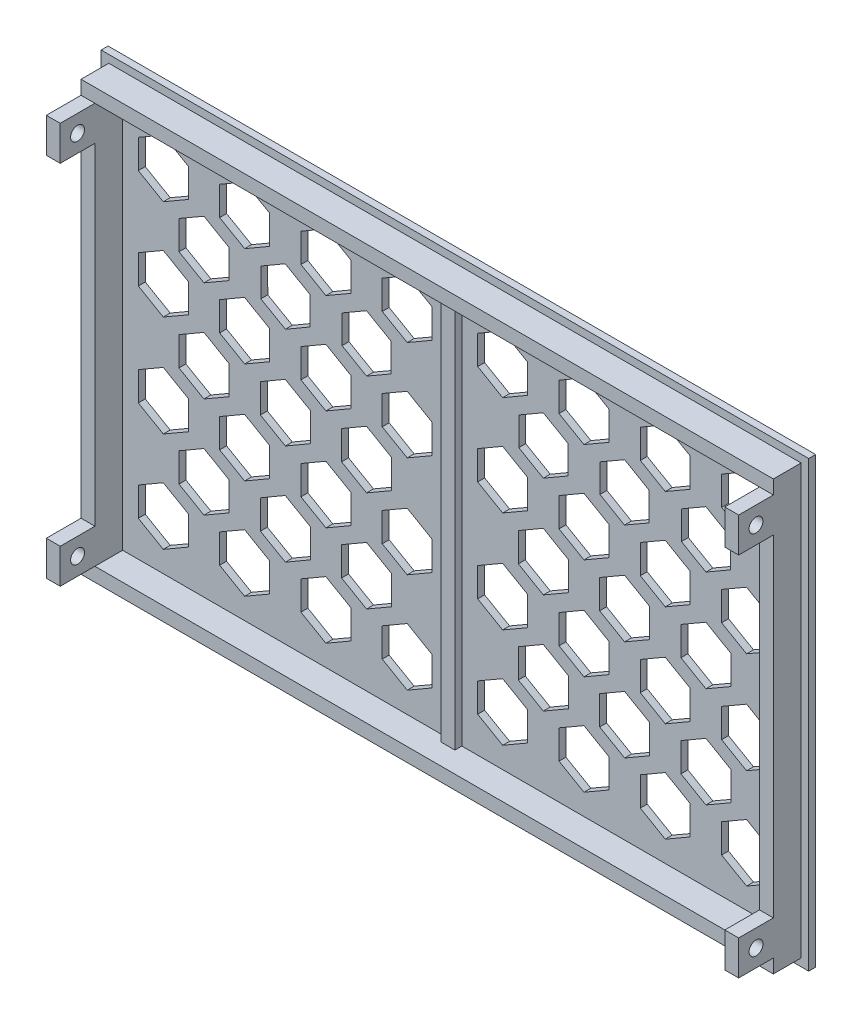
SolidWorks part; units mm, degrees
ref_plane "Спереди" through (0, 0, 0) normal (0, 0, 1) x (1, 0, 0)
ref_plane "Сверху" through (0, 0, 0) normal (0, 1, 0) x (1, 0, 0)
ref_plane "Справа" through (0, 0, 0) normal (1, 0, 0) x (0, 0, -1)
sketch "Эскиз1" plane through (0, 0, 0) normal (0, 0, 1) x (1, 0, 0)
  line L0 (-41.023, 20.2512) -> (60.977, 20.2512)
  line L1 (60.977, 20.2512) -> (60.977, -43.7488)
  line L2 (60.977, -43.7488) -> (-41.023, -43.7488)
  line L3 (-41.023, -43.7488) -> (-41.023, 20.2512)
  line L4 (-39.923, -42.6488) -> (-39.923, 19.1512)
  line L5 (-39.923, 19.1512) -> (59.877, 19.1512)
  line L6 (59.877, 19.1512) -> (59.877, -42.6488)
  line L7 (59.877, -42.6488) -> (-39.923, -42.6488)
  line L8 (-37.923, -40.6488) -> (-37.923, 17.1512)
  line L9 (-37.923, 17.1512) -> (57.877, 17.1512)
  line L10 (57.877, 17.1512) -> (57.877, -40.6488)
  line L11 (57.877, -40.6488) -> (-37.923, -40.6488)
  line L12 (57.877, -40.6488) -> (59.877, -40.6488)
  line L13 (59.877, -40.6488) -> (59.877, -35.6488)
  line L14 (59.877, -35.6488) -> (57.877, -35.6488)
  line L15 (57.877, -35.6488) -> (57.877, -40.6488)
  line L16 (57.877, 17.1512) -> (59.877, 17.1512)
  line L17 (59.877, 17.1512) -> (59.877, 12.1512)
  line L18 (59.877, 12.1512) -> (57.877, 12.1512)
  line L19 (57.877, 12.1512) -> (57.877, 17.1512)
  line L20 (-37.923, 17.1512) -> (-39.923, 17.1512)
  line L21 (-39.923, 17.1512) -> (-39.923, 12.1512)
  line L22 (-39.923, 12.1512) -> (-37.923, 12.1512)
  line L23 (-37.923, 12.1512) -> (-37.923, 17.1512)
  line L24 (-37.923, -40.6488) -> (-39.923, -40.6488)
  line L25 (-39.923, -40.6488) -> (-39.923, -35.6488)
  line L26 (-39.923, -35.6488) -> (-37.923, -35.6488)
  line L27 (-37.923, -35.6488) -> (-37.923, -40.6488)
  line L28 (9.977, 17.1512) -> (9.977, -40.6488)
  line L29 (10.977, 17.1512) -> (10.977, -40.6488)
  line L30 (8.977, 17.1512) -> (8.977, -40.6488)
  line L61 (-32.063, 5.7943) -> (-28.463, 7.8727)
  line L62 (-28.463, 7.8727) -> (-28.463, 12.0297)
  line L63 (-28.463, 12.0297) -> (-32.063, 14.1081)
  line L64 (-32.063, 14.1081) -> (-35.663, 12.0297)
  line L65 (-35.663, 12.0297) -> (-35.663, 7.8727)
  line L66 (-35.663, 7.8727) -> (-32.063, 5.7943)
  line L73 (-26.203, 6.9081) -> (-29.803, 4.8297)
  line L74 (-29.803, 4.8297) -> (-29.803, 0.6727)
  line L75 (-29.803, 0.6727) -> (-26.203, -1.4057)
  line L76 (-26.203, -1.4057) -> (-22.603, 0.6727)
  line L77 (-22.603, 0.6727) -> (-22.603, 4.8297)
  line L78 (-22.603, 4.8297) -> (-26.203, 6.9081)
  line L97 (-20.343, 14.1081) -> (-23.943, 12.0297)
  line L98 (-23.943, 12.0297) -> (-23.943, 7.8727)
  line L99 (-23.943, 7.8727) -> (-20.343, 5.7943)
  line L100 (-20.343, 5.7943) -> (-16.743, 7.8727)
  line L101 (-16.743, 7.8727) -> (-16.743, 12.0297)
  line L102 (-16.743, 12.0297) -> (-20.343, 14.1081)
  line L103 (-8.623, 14.1081) -> (-12.223, 12.0297)
  line L104 (-12.223, 12.0297) -> (-12.223, 7.8727)
  line L105 (-12.223, 7.8727) -> (-8.623, 5.7943)
  line L106 (-8.623, 5.7943) -> (-5.023, 7.8727)
  line L107 (-5.023, 7.8727) -> (-5.023, 12.0297)
  line L108 (-5.023, 12.0297) -> (-8.623, 14.1081)
  line L109 (3.097, 14.1081) -> (-0.503, 12.0297)
  line L110 (-0.503, 12.0297) -> (-0.503, 7.8727)
  line L111 (-0.503, 7.8727) -> (3.097, 5.7943)
  line L112 (3.097, 5.7943) -> (6.697, 7.8727)
  line L113 (6.697, 7.8727) -> (6.697, 12.0297)
  line L114 (6.697, 12.0297) -> (3.097, 14.1081)
  line L115 (-14.483, 6.8335) -> (-18.0134, 4.7837)
  line L116 (-18.0134, 4.7837) -> (-18.0034, 0.7014)
  line L117 (-18.0034, 0.7014) -> (-14.463, -1.3311)
  line L118 (-14.463, -1.3311) -> (-10.9326, 0.7187)
  line L119 (-10.9326, 0.7187) -> (-10.9426, 4.801)
  line L120 (-10.9426, 4.801) -> (-14.483, 6.8335)
  line L121 (-2.763, 6.8335) -> (-6.2984, 4.7924)
  line L122 (-6.2984, 4.7924) -> (-6.2984, 0.7101)
  line L123 (-6.2984, 0.7101) -> (-2.763, -1.3311)
  line L124 (-2.763, -1.3311) -> (0.7724, 0.7101)
  line L125 (0.7724, 0.7101) -> (0.7724, 4.7924)
  line L126 (0.7724, 4.7924) -> (-2.763, 6.8335)
  line L127 (-32.063, -0.2919) -> (-35.663, -2.3703)
  line L128 (-35.663, -2.3703) -> (-35.663, -6.5273)
  line L129 (-35.663, -6.5273) -> (-32.063, -8.6057)
  line L130 (-32.063, -8.6057) -> (-28.463, -6.5273)
  line L131 (-28.463, -6.5273) -> (-28.463, -2.3703)
  line L132 (-28.463, -2.3703) -> (-32.063, -0.2919)
  line L133 (-32.063, -14.8919) -> (-35.663, -16.9703)
  line L134 (-35.663, -16.9703) -> (-35.663, -21.1273)
  line L135 (-35.663, -21.1273) -> (-32.063, -23.2057)
  line L136 (-32.063, -23.2057) -> (-28.463, -21.1273)
  line L137 (-28.463, -21.1273) -> (-28.463, -16.9703)
  line L138 (-28.463, -16.9703) -> (-32.063, -14.8919)
  line L139 (-32.063, -29.2919) -> (-35.663, -31.3703)
  line L140 (-35.663, -31.3703) -> (-35.663, -35.5273)
  line L141 (-35.663, -35.5273) -> (-32.063, -37.6057)
  line L142 (-32.063, -37.6057) -> (-28.463, -35.5273)
  line L143 (-28.463, -35.5273) -> (-28.463, -31.3703)
  line L144 (-28.463, -31.3703) -> (-32.063, -29.2919)
  line L145 (-20.343, -29.2919) -> (-23.943, -31.3703)
  line L146 (-23.943, -31.3703) -> (-23.943, -35.5273)
  line L147 (-23.943, -35.5273) -> (-20.343, -37.6057)
  line L148 (-20.343, -37.6057) -> (-16.743, -35.5273)
  line L149 (-16.743, -35.5273) -> (-16.743, -31.3703)
  line L150 (-16.743, -31.3703) -> (-20.343, -29.2919)
  line L151 (-8.623, -29.2919) -> (-12.223, -31.3703)
  line L152 (-12.223, -31.3703) -> (-12.223, -35.5273)
  line L153 (-12.223, -35.5273) -> (-8.623, -37.6057)
  line L154 (-8.623, -37.6057) -> (-5.023, -35.5273)
  line L155 (-5.023, -35.5273) -> (-5.023, -31.3703)
  line L156 (-5.023, -31.3703) -> (-8.623, -29.2919)
  line L157 (3.097, -29.2919) -> (-0.503, -31.3703)
  line L158 (-0.503, -31.3703) -> (-0.503, -35.5273)
  line L159 (-0.503, -35.5273) -> (3.097, -37.6057)
  line L160 (3.097, -37.6057) -> (6.697, -35.5273)
  line L161 (6.697, -35.5273) -> (6.697, -31.3703)
  line L162 (6.697, -31.3703) -> (3.097, -29.2919)
  line L163 (16.857, -29.2919) -> (13.257, -31.3703)
  line L164 (13.257, -31.3703) -> (13.257, -35.5273)
  line L165 (13.257, -35.5273) -> (16.857, -37.6057)
  line L166 (16.857, -37.6057) -> (20.457, -35.5273)
  line L167 (20.457, -35.5273) -> (20.457, -31.3703)
  line L168 (20.457, -31.3703) -> (16.857, -29.2919)
  line L169 (28.577, -29.2919) -> (24.977, -31.3703)
  line L170 (24.977, -31.3703) -> (24.977, -35.5273)
  line L171 (24.977, -35.5273) -> (28.577, -37.6057)
  line L172 (28.577, -37.6057) -> (32.177, -35.5273)
  line L173 (32.177, -35.5273) -> (32.177, -31.3703)
  line L174 (32.177, -31.3703) -> (28.577, -29.2919)
  line L175 (-20.343, -14.8919) -> (-23.943, -16.9703)
  line L176 (-23.943, -16.9703) -> (-23.943, -21.1273)
  line L177 (-23.943, -21.1273) -> (-20.343, -23.2057)
  line L178 (-20.343, -23.2057) -> (-16.743, -21.1273)
  line L179 (-16.743, -21.1273) -> (-16.743, -16.9703)
  line L180 (-16.743, -16.9703) -> (-20.343, -14.8919)
  line L181 (-20.343, -0.2919) -> (-23.943, -2.3703)
  line L182 (-23.943, -2.3703) -> (-23.943, -6.5273)
  line L183 (-23.943, -6.5273) -> (-20.343, -8.6057)
  line L184 (-20.343, -8.6057) -> (-16.743, -6.5273)
  line L185 (-16.743, -6.5273) -> (-16.743, -2.3703)
  line L186 (-16.743, -2.3703) -> (-20.343, -0.2919)
  line L187 (-8.623, -0.2919) -> (-12.223, -2.3703)
  line L188 (-12.223, -2.3703) -> (-12.223, -6.5273)
  line L189 (-12.223, -6.5273) -> (-8.623, -8.6057)
  line L190 (-8.623, -8.6057) -> (-5.023, -6.5273)
  line L191 (-5.023, -6.5273) -> (-5.023, -2.3703)
  line L192 (-5.023, -2.3703) -> (-8.623, -0.2919)
  line L193 (3.097, -0.2919) -> (-0.503, -2.3703)
  line L194 (-0.503, -2.3703) -> (-0.503, -6.5273)
  line L195 (-0.503, -6.5273) -> (3.097, -8.6057)
  line L196 (3.097, -8.6057) -> (6.697, -6.5273)
  line L197 (6.697, -6.5273) -> (6.697, -2.3703)
  line L198 (6.697, -2.3703) -> (3.097, -0.2919)
  line L199 (16.857, -0.2919) -> (13.257, -2.3703)
  line L200 (13.257, -2.3703) -> (13.257, -6.5273)
  line L201 (13.257, -6.5273) -> (16.857, -8.6057)
  line L202 (16.857, -8.6057) -> (20.457, -6.5273)
  line L203 (20.457, -6.5273) -> (20.457, -2.3703)
  line L204 (20.457, -2.3703) -> (16.857, -0.2919)
  line L205 (28.577, -0.2919) -> (24.977, -2.3703)
  line L206 (24.977, -2.3703) -> (24.977, -6.5273)
  line L207 (24.977, -6.5273) -> (28.577, -8.6057)
  line L208 (28.577, -8.6057) -> (32.177, -6.5273)
  line L209 (32.177, -6.5273) -> (32.177, -2.3703)
  line L210 (32.177, -2.3703) -> (28.577, -0.2919)
  line L211 (40.297, -0.2919) -> (36.697, -2.3703)
  line L212 (36.697, -2.3703) -> (36.697, -6.5273)
  line L213 (36.697, -6.5273) -> (40.297, -8.6057)
  line L214 (40.297, -8.6057) -> (43.897, -6.5273)
  line L215 (43.897, -6.5273) -> (43.897, -2.3703)
  line L216 (43.897, -2.3703) -> (40.297, -0.2919)
  line L217 (52.017, -0.2919) -> (48.417, -2.3703)
  line L218 (48.417, -2.3703) -> (48.417, -6.5273)
  line L219 (48.417, -6.5273) -> (52.017, -8.6057)
  line L220 (52.017, -8.6057) -> (55.617, -6.5273)
  line L221 (55.617, -6.5273) -> (55.617, -2.3703)
  line L222 (55.617, -2.3703) -> (52.017, -0.2919)
  line L223 (40.297, -29.2919) -> (36.697, -31.3703)
  line L224 (36.697, -31.3703) -> (36.697, -35.5273)
  line L225 (36.697, -35.5273) -> (40.297, -37.6057)
  line L226 (40.297, -37.6057) -> (43.897, -35.5273)
  line L227 (43.897, -35.5273) -> (43.897, -31.3703)
  line L228 (43.897, -31.3703) -> (40.297, -29.2919)
  line L229 (52.017, -29.2919) -> (48.417, -31.3703)
  line L230 (48.417, -31.3703) -> (48.417, -35.5273)
  line L231 (48.417, -35.5273) -> (52.017, -37.6057)
  line L232 (52.017, -37.6057) -> (55.617, -35.5273)
  line L233 (55.617, -35.5273) -> (55.617, -31.3703)
  line L234 (55.617, -31.3703) -> (52.017, -29.2919)
  line L235 (-8.623, -14.8919) -> (-12.223, -16.9703)
  line L236 (-12.223, -16.9703) -> (-12.223, -21.1273)
  line L237 (-12.223, -21.1273) -> (-8.623, -23.2057)
  line L238 (-8.623, -23.2057) -> (-5.023, -21.1273)
  line L239 (-5.023, -21.1273) -> (-5.023, -16.9703)
  line L240 (-5.023, -16.9703) -> (-8.623, -14.8919)
  line L241 (3.097, -14.8919) -> (-0.503, -16.9703)
  line L242 (-0.503, -16.9703) -> (-0.503, -21.1273)
  line L243 (-0.503, -21.1273) -> (3.097, -23.2057)
  line L244 (3.097, -23.2057) -> (6.697, -21.1273)
  line L245 (6.697, -21.1273) -> (6.697, -16.9703)
  line L246 (6.697, -16.9703) -> (3.097, -14.8919)
  line L247 (16.857, -14.8919) -> (13.257, -16.9703)
  line L248 (13.257, -16.9703) -> (13.257, -21.1273)
  line L249 (13.257, -21.1273) -> (16.857, -23.2057)
  line L250 (16.857, -23.2057) -> (20.457, -21.1273)
  line L251 (20.457, -21.1273) -> (20.457, -16.9703)
  line L252 (20.457, -16.9703) -> (16.857, -14.8919)
  line L253 (28.577, -14.8919) -> (24.977, -16.9703)
  line L254 (24.977, -16.9703) -> (24.977, -21.1273)
  line L255 (24.977, -21.1273) -> (28.577, -23.2057)
  line L256 (28.577, -23.2057) -> (32.177, -21.1273)
  line L257 (32.177, -21.1273) -> (32.177, -16.9703)
  line L258 (32.177, -16.9703) -> (28.577, -14.8919)
  line L259 (40.297, -14.8919) -> (36.697, -16.9703)
  line L260 (36.697, -16.9703) -> (36.697, -21.1273)
  line L261 (36.697, -21.1273) -> (40.297, -23.2057)
  line L262 (40.297, -23.2057) -> (43.897, -21.1273)
  line L263 (43.897, -21.1273) -> (43.897, -16.9703)
  line L264 (43.897, -16.9703) -> (40.297, -14.8919)
  line L265 (52.017, -14.8919) -> (48.417, -16.9703)
  line L266 (48.417, -16.9703) -> (48.417, -21.1273)
  line L267 (48.417, -21.1273) -> (52.017, -23.2057)
  line L268 (52.017, -23.2057) -> (55.617, -21.1273)
  line L269 (55.617, -21.1273) -> (55.617, -16.9703)
  line L270 (55.617, -16.9703) -> (52.017, -14.8919)
  line L271 (22.717, 6.8335) -> (19.1816, 4.7924)
  line L272 (19.1816, 4.7924) -> (19.1816, 0.7101)
  line L273 (19.1816, 0.7101) -> (22.717, -1.3311)
  line L274 (22.717, -1.3311) -> (26.2524, 0.7101)
  line L275 (26.2524, 0.7101) -> (26.2524, 4.7924)
  line L276 (26.2524, 4.7924) -> (22.717, 6.8335)
  line L277 (34.437, 6.8335) -> (30.8966, 4.801)
  line L278 (30.8966, 4.801) -> (30.8866, 0.7187)
  line L279 (30.8866, 0.7187) -> (34.417, -1.3311)
  line L280 (34.417, -1.3311) -> (37.9574, 0.7014)
  line L281 (37.9574, 0.7014) -> (37.9674, 4.7837)
  line L282 (37.9674, 4.7837) -> (34.437, 6.8335)
  line L283 (46.157, 6.8335) -> (42.6216, 4.7924)
  line L284 (42.6216, 4.7924) -> (42.6216, 0.7101)
  line L285 (42.6216, 0.7101) -> (46.157, -1.3311)
  line L286 (46.157, -1.3311) -> (49.6924, 0.7101)
  line L287 (49.6924, 0.7101) -> (49.6924, 4.7924)
  line L288 (49.6924, 4.7924) -> (46.157, 6.8335)
  line L289 (16.857, 14.1081) -> (13.257, 12.0297)
  line L290 (13.257, 12.0297) -> (13.257, 7.8727)
  line L291 (13.257, 7.8727) -> (16.857, 5.7943)
  line L292 (16.857, 5.7943) -> (20.457, 7.8727)
  line L293 (20.457, 7.8727) -> (20.457, 12.0297)
  line L294 (20.457, 12.0297) -> (16.857, 14.1081)
  line L295 (28.577, 14.1081) -> (24.977, 12.0297)
  line L296 (24.977, 12.0297) -> (24.977, 7.8727)
  line L297 (24.977, 7.8727) -> (28.577, 5.7943)
  line L298 (28.577, 5.7943) -> (32.177, 7.8727)
  line L299 (32.177, 7.8727) -> (32.177, 12.0297)
  line L300 (32.177, 12.0297) -> (28.577, 14.1081)
  line L301 (40.297, 14.1081) -> (36.697, 12.0297)
  line L302 (36.697, 12.0297) -> (36.697, 7.8727)
  line L303 (36.697, 7.8727) -> (40.297, 5.7943)
  line L304 (40.297, 5.7943) -> (43.897, 7.8727)
  line L305 (43.897, 7.8727) -> (43.897, 12.0297)
  line L306 (43.897, 12.0297) -> (40.297, 14.1081)
  line L307 (52.017, 14.1081) -> (48.417, 12.0297)
  line L308 (48.417, 12.0297) -> (48.417, 7.8727)
  line L309 (48.417, 7.8727) -> (52.017, 5.7943)
  line L310 (52.017, 5.7943) -> (55.617, 7.8727)
  line L311 (55.617, 7.8727) -> (55.617, 12.0297)
  line L312 (55.617, 12.0297) -> (52.017, 14.1081)
  line L313 (-26.203, -7.5919) -> (-29.803, -9.6703)
  line L314 (-29.803, -9.6703) -> (-29.803, -13.8273)
  line L315 (-29.803, -13.8273) -> (-26.203, -15.9057)
  line L316 (-26.203, -15.9057) -> (-22.603, -13.8273)
  line L317 (-22.603, -13.8273) -> (-22.603, -9.6703)
  line L318 (-22.603, -9.6703) -> (-26.203, -7.5919)
  line L319 (-26.203, -22.0919) -> (-29.803, -24.1703)
  line L320 (-29.803, -24.1703) -> (-29.803, -28.3273)
  line L321 (-29.803, -28.3273) -> (-26.203, -30.4057)
  line L322 (-26.203, -30.4057) -> (-22.603, -28.3273)
  line L323 (-22.603, -28.3273) -> (-22.603, -24.1703)
  line L324 (-22.603, -24.1703) -> (-26.203, -22.0919)
  line L325 (-14.483, -7.5919) -> (-18.078, -9.679)
  line L326 (-18.078, -9.679) -> (-18.068, -13.8359)
  line L327 (-18.068, -13.8359) -> (-14.463, -15.9057)
  line L328 (-14.463, -15.9057) -> (-10.868, -13.8186)
  line L329 (-10.868, -13.8186) -> (-10.878, -9.6617)
  line L330 (-10.878, -9.6617) -> (-14.483, -7.5919)
  line L331 (-2.763, -7.5919) -> (-6.363, -9.6703)
  line L332 (-6.363, -9.6703) -> (-6.363, -13.8273)
  line L333 (-6.363, -13.8273) -> (-2.763, -15.9057)
  line L334 (-2.763, -15.9057) -> (0.837, -13.8273)
  line L335 (0.837, -13.8273) -> (0.837, -9.6703)
  line L336 (0.837, -9.6703) -> (-2.763, -7.5919)
  line L337 (22.717, -7.5919) -> (19.117, -9.6703)
  line L338 (19.117, -9.6703) -> (19.117, -13.8273)
  line L339 (19.117, -13.8273) -> (22.717, -15.9057)
  line L340 (22.717, -15.9057) -> (26.317, -13.8273)
  line L341 (26.317, -13.8273) -> (26.317, -9.6703)
  line L342 (26.317, -9.6703) -> (22.717, -7.5919)
  line L343 (34.437, -7.5919) -> (30.837, -9.6703)
  line L344 (30.837, -9.6703) -> (30.837, -13.8273)
  line L345 (30.837, -13.8273) -> (34.437, -15.9057)
  line L346 (34.437, -15.9057) -> (38.037, -13.8273)
  line L347 (38.037, -13.8273) -> (38.037, -9.6703)
  line L348 (38.037, -9.6703) -> (34.437, -7.5919)
  line L349 (46.157, -7.5919) -> (42.557, -9.6703)
  line L350 (42.557, -9.6703) -> (42.557, -13.8273)
  line L351 (42.557, -13.8273) -> (46.157, -15.9057)
  line L352 (46.157, -15.9057) -> (49.757, -13.8273)
  line L353 (49.757, -13.8273) -> (49.757, -9.6703)
  line L354 (49.757, -9.6703) -> (46.157, -7.5919)
  line L355 (46.157, -22.0919) -> (42.557, -24.1703)
  line L356 (42.557, -24.1703) -> (42.557, -28.3273)
  line L357 (42.557, -28.3273) -> (46.157, -30.4057)
  line L358 (46.157, -30.4057) -> (49.757, -28.3273)
  line L359 (49.757, -28.3273) -> (49.757, -24.1703)
  line L360 (49.757, -24.1703) -> (46.157, -22.0919)
  line L361 (34.437, -22.0919) -> (30.837, -24.1703)
  line L362 (30.837, -24.1703) -> (30.837, -28.3273)
  line L363 (30.837, -28.3273) -> (34.437, -30.4057)
  line L364 (34.437, -30.4057) -> (38.037, -28.3273)
  line L365 (38.037, -28.3273) -> (38.037, -24.1703)
  line L366 (38.037, -24.1703) -> (34.437, -22.0919)
  line L367 (22.717, -22.0919) -> (19.117, -24.1703)
  line L368 (19.117, -24.1703) -> (19.117, -28.3273)
  line L369 (19.117, -28.3273) -> (22.717, -30.4057)
  line L370 (22.717, -30.4057) -> (26.317, -28.3273)
  line L371 (26.317, -28.3273) -> (26.317, -24.1703)
  line L372 (26.317, -24.1703) -> (22.717, -22.0919)
  line L373 (-14.483, -22.0919) -> (-18.078, -24.179)
  line L374 (-18.078, -24.179) -> (-18.068, -28.3359)
  line L375 (-18.068, -28.3359) -> (-14.463, -30.4057)
  line L376 (-14.463, -30.4057) -> (-10.868, -28.3186)
  line L377 (-10.868, -28.3186) -> (-10.878, -24.1617)
  line L378 (-10.878, -24.1617) -> (-14.483, -22.0919)
  line L379 (-2.763, -22.0919) -> (-6.363, -24.1703)
  line L380 (-6.363, -24.1703) -> (-6.363, -28.3273)
  line L381 (-6.363, -28.3273) -> (-2.763, -30.4057)
  line L382 (-2.763, -30.4057) -> (0.837, -28.3273)
  line L383 (0.837, -28.3273) -> (0.837, -24.1703)
  line L384 (0.837, -24.1703) -> (-2.763, -22.0919)
  circle A0 centre (-32.063, 9.9512) radius 3.6 construction
  circle A1 centre (-26.203, 2.7512) radius 3.6 construction
  circle A2 centre (-20.343, 9.9512) radius 3.6 construction
  circle A3 centre (-8.623, 9.9512) radius 3.6 construction
  circle A4 centre (3.097, 9.9512) radius 3.6 construction
  circle A5 centre (-14.473, 2.7512) radius 3.5354 construction
  circle A6 centre (-2.763, 2.7512) radius 3.5354 construction
  circle A7 centre (-32.063, -4.4488) radius 3.6 construction
  circle A8 centre (-32.063, -19.0488) radius 3.6 construction
  circle A9 centre (-32.063, -33.4488) radius 3.6 construction
  circle A10 centre (-20.343, -33.4488) radius 3.6 construction
  circle A11 centre (-8.623, -33.4488) radius 3.6 construction
  circle A12 centre (3.097, -33.4488) radius 3.6 construction
  circle A13 centre (16.857, -33.4488) radius 3.6 construction
  circle A14 centre (28.577, -33.4488) radius 3.6 construction
  circle A15 centre (-20.343, -19.0488) radius 3.6 construction
  circle A16 centre (-20.343, -4.4488) radius 3.6 construction
  circle A17 centre (-8.623, -4.4488) radius 3.6 construction
  circle A18 centre (3.097, -4.4488) radius 3.6 construction
  circle A19 centre (16.857, -4.4488) radius 3.6 construction
  circle A20 centre (28.577, -4.4488) radius 3.6 construction
  circle A21 centre (40.297, -4.4488) radius 3.6 construction
  circle A22 centre (52.017, -4.4488) radius 3.6 construction
  circle A23 centre (40.297, -33.4488) radius 3.6 construction
  circle A24 centre (52.017, -33.4488) radius 3.6 construction
  circle A25 centre (-8.623, -19.0488) radius 3.6 construction
  circle A26 centre (3.097, -19.0488) radius 3.6 construction
  circle A27 centre (16.857, -19.0488) radius 3.6 construction
  circle A28 centre (28.577, -19.0488) radius 3.6 construction
  circle A29 centre (40.297, -19.0488) radius 3.6 construction
  circle A30 centre (52.017, -19.0488) radius 3.6 construction
  circle A31 centre (22.717, 2.7512) radius 3.5354 construction
  circle A32 centre (34.427, 2.7512) radius 3.5354 construction
  circle A33 centre (46.157, 2.7512) radius 3.5354 construction
  circle A34 centre (16.857, 9.9512) radius 3.6 construction
  circle A35 centre (28.577, 9.9512) radius 3.6 construction
  circle A36 centre (40.297, 9.9512) radius 3.6 construction
  circle A37 centre (52.017, 9.9512) radius 3.6 construction
  circle A38 centre (-26.203, -11.7488) radius 3.6 construction
  circle A39 centre (-26.203, -26.2488) radius 3.6 construction
  circle A40 centre (-14.473, -11.7488) radius 3.6 construction
  circle A41 centre (-2.763, -11.7488) radius 3.6 construction
  circle A42 centre (22.717, -11.7488) radius 3.6 construction
  circle A43 centre (34.437, -11.7488) radius 3.6 construction
  circle A44 centre (46.157, -11.7488) radius 3.6 construction
  circle A45 centre (46.157, -26.2488) radius 3.6 construction
  circle A46 centre (34.437, -26.2488) radius 3.6 construction
  circle A47 centre (22.717, -26.2488) radius 3.6 construction
  circle A48 centre (-14.473, -26.2488) radius 3.6 construction
  circle A49 centre (-2.763, -26.2488) radius 3.6 construction
  dimension "D1" = 64
  dimension "D2" = 102
  dimension "D3" = 1.1
  dimension "D4" = 1.1
  dimension "D5" = 1.1
  dimension "D6" = 1.1
  dimension "D7" = 2
  dimension "D8" = 2
  dimension "D9" = 2
  dimension "D10" = 2
  dimension "D11" = 5
  dimension "D12" = 5
  dimension "D13" = 5
  dimension "D14" = 5
  dimension "D15" = 1
  dimension "D16" = 1
  dimension "D19" = 57.8
  dimension "D25" = 46.9
extrude "Бобышка-Вытянуть1" add sketch "Эскиз1" along normal blind 1 contours L1 L2 L3 L0
extrude "Бобышка-Вытянуть3" add sketch "Эскиз1<4>" along normal blind 5 contours L4 L26 L8 L22 | L20 L9 L16 L6 L5 L4 | L11 L24 L4 L7 L6 L12 | L6 L18 L10 L14 region at (9.977, -41.6488, 0) region at (-38.923, -11.7488, 0) region at (58.877, -11.7488, 0) region at (9.977, 18.1512, 0)
sketch "Эскиз1<4>" plane through (0, 0, 0) normal (0, 0, 1) x (1, 0, 0) same geometry as "Эскиз1"
extrude "Бобышка-Вытянуть4" add sketch "Эскиз1<5>" along normal blind 10 contours L26 L4 L24 L8 | L6 L14 L10 L12 | L18 L6 L16 L10 | L4 L22 L8 L20 region at (-38.923, -38.1488, 0) region at (58.877, -38.1488, 0) region at (-38.923, 14.6512, 0) region at (58.877, 14.6512, 0)
sketch "Эскиз1<5>" plane through (0, 0, 0) normal (0, 0, 1) x (1, 0, 0) same geometry as "Эскиз1"
extrude "Бобышка-Вытянуть5" add sketch "Эскиз1<7>" along normal blind 2 contours L29 L9 L28 L11 | L9 L30 L11 L28 region at (9.477, -11.7488, 0) region at (10.477, -11.7488, 0)
sketch "Эскиз1<7>" plane through (0, 0, 0) normal (0, 0, 1) x (1, 0, 0) same geometry as "Эскиз1"
extrude "Вырез-Вытянуть3" cut sketch "Эскиз1<8>" along normal blind 1 and the other way blind 1 contours L65 L66 L61 L62 L63 L64 | L101 L102 L97 L98 L99 L100 | L107 L108 L103 L104 L105 L106 | L113 L114 L109 L110 L111 L112 | L293 L294 L289 L290 L291 L292 | L299 L300 L295 L296 L297 L298 | L305 L306 L301 L302 L303 L304 | L311 L312 L307 L308 L309 L310 | L287 L288 L283 L284 L285 L286 | L281 L282 L277 L278 L279 L280 | L275 L276 L271 L272 L273 L274 | L125 L126 L121 L122 L123 L124 | L119 L120 L115 L116 L117 L118 | L77 L78 L73 L74 L75 L76 | L131 L132 L127 L128 L129 L130 | L185 L186 L181 L182 L183 L184 | L191 L192 L187 L188 L189 L190 | L329 L330 L325 L326 L327 L328 | L317 L318 L313 L314 L315 L316 | L137 L138 L133 L134 L135 L136 | L179 L180 L175 L176 L177 L178 | L323 L324 L319 L320 L321 L322 | L143 L144 L139 L140 L141 L142 | L149 L150 L145 L146 L147 L148 | L377 L378 L373 L374 L375 L376 | L239 L240 L235 L236 L237 L238 | L335 L336 L331 L332 L333 L334 | L197 L198 L193 L194 L195 L196 | L203 L204 L199 L200 L201 L202 | L245 L246 L241 L242 L243 L244 | L383 L384 L379 L380 L381 L382 | L155 L156 L151 L152 L153 L154 | L161 L162 L157 L158 L159 L160 | L251 L252 L247 L248 L249 L250 | L341 L342 L337 L338 L339 L340 | L209 L210 L205 L206 L207 L208 | L215 L216 L211 L212 L213 L214 | L221 L222 L217 L218 L219 L220 | L353 L354 L349 L350 L351 L352 | L347 L348 L343 L344 L345 L346 | L257 L258 L253 L254 L255 L256 | L263 L264 L259 L260 L261 L262 | L269 L270 L265 L266 L267 L268 | L359 L360 L355 L356 L357 L358 | L365 L366 L361 L362 L363 L364 | L371 L372 L367 L368 L369 L370 | L167 L168 L163 L164 L165 L166 | L173 L174 L169 L170 L171 L172 | L227 L228 L223 L224 L225 L226 | L233 L234 L229 L230 L231 L232 region at (-32.063, 9.9512, 0) region at (-26.203, 2.7512, 0) region at (-20.343, 9.9512, 0) region at (-8.623, 9.9512, 0) region at (3.097, 9.9512, 0) region at (-14.473, 2.7512, 0) region at (-2.763, 2.7512, 0) region at (-32.063, -4.4488, 0) region at (-32.063, -19.0488, 0) region at (-32.063, -33.4488, 0) region at (-20.343, -33.4488, 0) region at (-8.623, -33.4488, 0) region at (3.097, -33.4488, 0) region at (16.857, -33.4488, 0) region at (28.577, -33.4488, 0) region at (-20.343, -19.0488, 0) region at (-20.343, -4.4488, 0) region at (-8.623, -4.4488, 0) region at (3.097, -4.4488, 0) region at (16.857, -4.4488, 0) region at (28.577, -4.4488, 0) region at (40.297, -4.4488, 0) region at (52.017, -4.4488, 0) region at (40.297, -33.4488, 0) region at (52.017, -33.4488, 0) region at (-8.623, -19.0488, 0) region at (3.097, -19.0488, 0) region at (16.857, -19.0488, 0) region at (28.577, -19.0488, 0) region at (40.297, -19.0488, 0) region at (52.017, -19.0488, 0) region at (22.717, 2.7512, 0) region at (34.427, 2.7512, 0) region at (46.157, 2.7512, 0) region at (16.857, 9.9512, 0) region at (28.577, 9.9512, 0) region at (40.297, 9.9512, 0) region at (52.017, 9.9512, 0) region at (-26.203, -11.7488, 0) region at (-26.203, -26.2488, 0) region at (-14.473, -11.7488, 0) region at (-2.763, -11.7488, 0) region at (22.717, -11.7488, 0) region at (34.437, -11.7488, 0) region at (46.157, -11.7488, 0) region at (46.157, -26.2488, 0) region at (34.437, -26.2488, 0) region at (22.717, -26.2488, 0) region at (-14.473, -26.2488, 0) region at (-2.763, -26.2488, 0)
sketch "Эскиз1<8>" plane through (0, 0, 0) normal (0, 0, 1) x (1, 0, 0) same geometry as "Эскиз1"
sketch "Эскиз2" plane through (59.877, 0, 0) normal (1, 0, 0) x (0, 0, -1)
  line L0 (-5, 17.1512) -> (-5, 12.1512)
  line L3 (-5, -40.6488) -> (-5, -35.6488)
  circle A0 centre (-7.5, 14.6512) radius 1
  circle A1 centre (-7.5, -38.1488) radius 1
extrude "Вырез-Вытянуть4" cut sketch "Эскиз2" against normal blind 100 contours A0 | A1 region at (59.877, 14.6512, 7.5) region at (59.877, -38.1488, 7.5)
